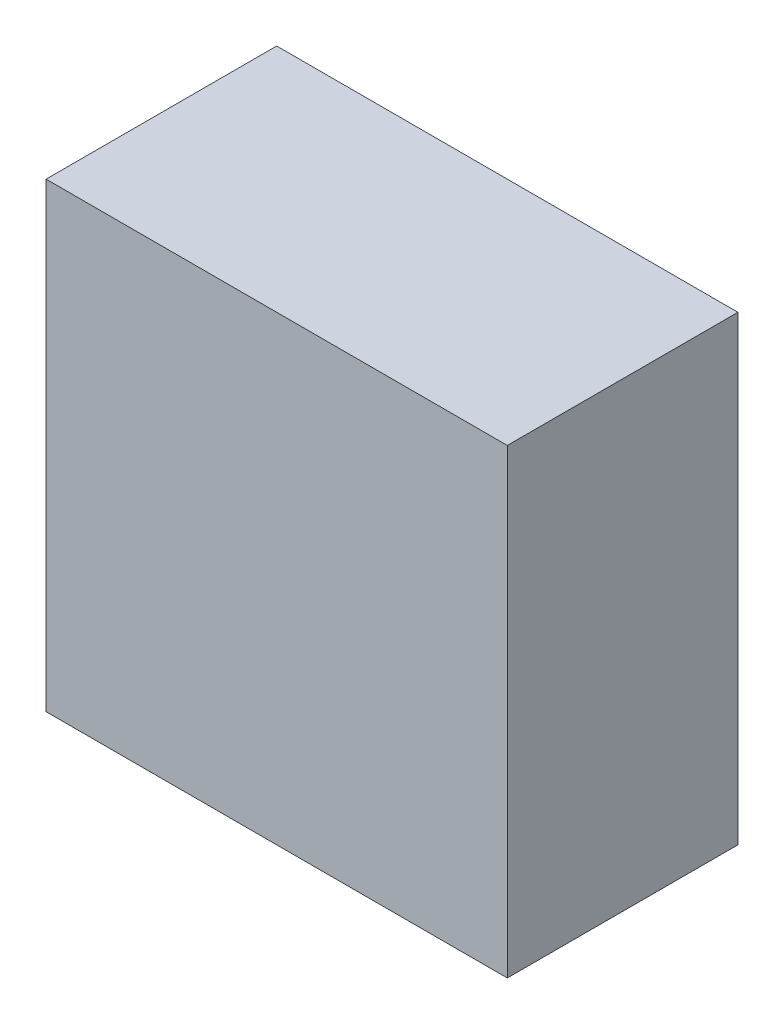
SolidWorks part; units mm, degrees
ref_plane "前视基准面" through (0, 0, 0) normal (0, 0, 1) x (1, 0, 0)
ref_plane "上视基准面" through (0, 0, 0) normal (0, 1, 0) x (1, 0, 0)
ref_plane "右视基准面" through (0, 0, 0) normal (1, 0, 0) x (0, 0, -1)
other "Configuration Table"
sketch "草图1" plane through (0, 0, 0) normal (0, 0, 1) x (1, 0, 0)
  line L1 (0, 0) -> (20, 0)
  line L2 (0, 0) -> (0, 20)
  line L3 (0, 20) -> (20, 20)
  line L4 (20, 0) -> (20, 20)
extrude "BaseBox" add sketch "草图1" along normal blind 10
sketch "草图2" plane through (0, 0, 10) normal (0, 0, 1) x (1, 0, 0)
  circle A0 centre (10, 10) radius 2
extrude "FromOffsetReverseBoss" add sketch "草图2" along normal blind 5 from offset 5 offset against normal yes
